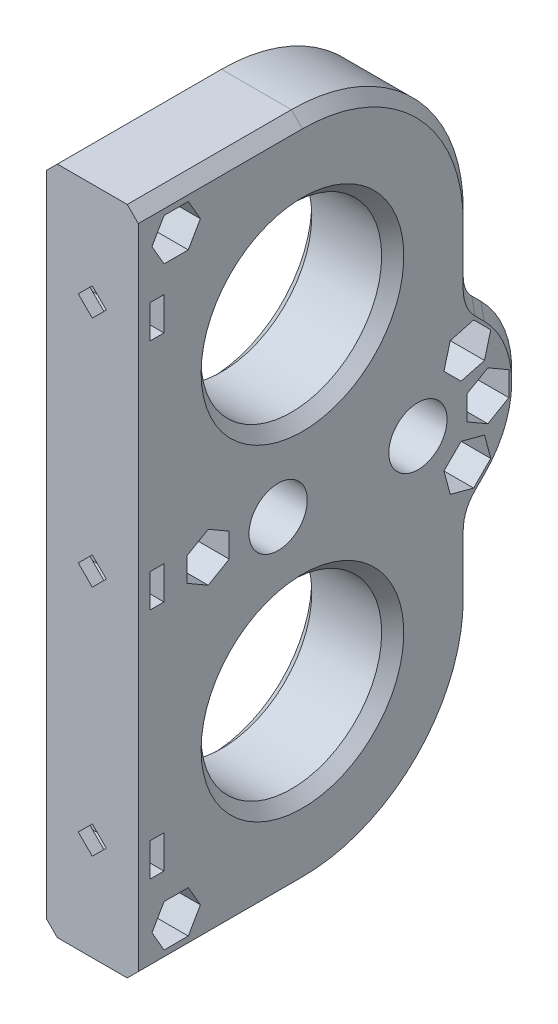
SolidWorks part; units mm, degrees
ref_plane "1" through (0, 0, 0) normal (0, 0, 1) x (1, 0, 0)
ref_plane "2" through (0, 0, 0) normal (0, 1, 0) x (1, 0, 0)
ref_plane "3" through (0, 0, 0) normal (1, 0, 0) x (0, 0, -1)
ref_plane "Front Plane" through (0, 0, 0) normal (0, -1, 0) x (1, 0, 0)
ref_plane "Right Plane" through (0, 0, 0) normal (1, 0, 0) x (0, 1, 0)
ref_plane "Top Plane" through (0, 0, 0) normal (0, 0, 1) x (1, 0, 0)
imported_body "Imported1" [suppressed]
move or copy body "Body-Move/Copy1" [suppressed] bodies to move or copy 110 copy no rotation origin (0, 0, 0) rotation axis (1, 0, 0) rotation angle 90
move or copy body "Body-Move/Copy2" [suppressed] bodies to move or copy 111 copy no translate (0, 0, 4.1741) parameters "D1"=0, "D2"=0, "D3"=4.1741
move or copy body "Body-Move/Copy3" [suppressed] bodies to move or copy 112 copy no translate (0, 0, 80) parameters "D1"=0, "D2"=0, "D3"=80
sketch "Sketch1" plane through (0, 0, 0) normal (1, 0, 0) x (0, 1, 0)
  line L0 (-28, 0) -> (0, -91.8259) construction
  line L1 (0, -91.8259) -> (28, 0) construction
  line L2 (-28, 0) -> (28, 0) construction
  line L3 (0, -91.8259) -> (0, -105.6378) construction
  line L4 (-28, -22.5) -> (-28, 0) construction
  line L11 (-8.4853, -28.3112) -> (-4.9497, -24.7757) construction
  line L12 (0, -31.8259) -> (0, -26.8259) construction
  line L13 (8.4853, -28.3112) -> (4.9497, -24.7757) construction
  line L14 (-47.4856, 11.25) -> (-28, 0) construction
  circle A0 centre (-28, 0) radius 22.5 construction
  arc A1 (-28, 0) -> (28, 0) centre (0, -91.8259) cw construction
  circle A2 centre (0, -19.8259) radius 7 construction
  circle A3 centre (0, 16.1741) radius 2 construction
  circle A7 centre (-8.4853, -28.3112) radius 2 construction
  circle A8 centre (0, -31.8259) radius 2 construction
  circle A9 centre (8.4853, -28.3112) radius 2 construction
  circle A10 centre (-47.4856, 11.25) radius 1.25 construction
  dimension "D1" = 96
  dimension "D2" = 45
  dimension "D4" = 108
  dimension "D5" = 4
  dimension "D6" = 72
  dimension "D7" = 14
  dimension "D10" = 12
  dimension "D12" = 2.5
  dimension "D3" = 56
  dimension "D8" = 45
  dimension "D9" = 45
  dimension "D11" = 120
sketch "Sketch2" plane through (0, 0, 0) normal (1, 0, 0) x (0, 1, 0)
  line L6 (-12.7279, -32.5538) -> (-14.3173, -30.9645)
  line L7 (0, 28.1741) -> (0, -37.8259)
  line L8 (0, -91.8259) -> (0, -105.6378) construction
  line L9 (-28, -29.5) -> (-17.8528, -29.5)
  line L10 (-57.5, 0) -> (-57.5, 28.1741)
  line L11 (-57.5, 28.1741) -> (0, 28.1741)
  circle A2 centre (0, -19.8259) radius 7 construction
  arc A3 (-57.5, 0) -> (-28, -29.5) centre (-28, 0) ccw
  arc A4 (0, -37.8259) -> (-12.7279, -32.5538) centre (0, -19.8259) cw
  circle A5 centre (-28, 0) radius 22.5 construction
  arc A6 (-17.8528, -29.5) -> (-14.3173, -30.9645) centre (-17.8528, -34.5) cw
  point P5 (-51.2991, 11.1306)
  dimension "D2" = 18
  dimension "D3" = 57.5
  dimension "D4" = 5
  dimension "D5" = 48
  dimension "D1" = 45
extrude "Boss-Extrude1" add sketch "Sketch2" against normal mid plane 16 separate body
sketch "Sketch9" plane through (0, 0, 0) normal (1, 0, 0) x (0, 1, 0)
  line L0 (0, 4.1741) -> (0, -19.8259) construction
  circle A5 centre (0, 4.1741) radius 5
  circle A6 centre (0, -19.8259) radius 5
  arc A7 (28, 0) -> (-28, 0) centre (0, -91.8259) ccw construction
  dimension "D2" = 96
  dimension "D1" = 10
  dimension "D3" = 24
extrude "Cut-Extrude1" cut sketch "Sketch9" along normal through all both and the other way through all from surface starting at face at (-8, -24.2983, -13.8775)
sketch "Sketch10" plane through (0, 0, 0) normal (1, 0, 0) x (0, 1, 0)
  line L0 (0, -91.8259) -> (0, -105.6378) construction
  line L1 (2.0785, 12.5741) -> (4.1569, 16.1741)
  line L2 (4.1569, 16.1741) -> (2.0785, 19.7741)
  line L3 (2.0785, 19.7741) -> (-2.0785, 19.7741)
  line L4 (-2.0785, 19.7741) -> (-4.1569, 16.1741)
  line L5 (-4.1569, 16.1741) -> (-2.0785, 12.5741)
  line L6 (-2.0785, 12.5741) -> (2.0785, 12.5741)
  line L7 (-5.5459, -31.2506) -> (-4.47, -27.2353)
  line L8 (-4.47, -27.2353) -> (-7.4094, -24.2959)
  line L9 (-7.4094, -24.2959) -> (-11.4247, -25.3718)
  line L10 (-11.4247, -25.3718) -> (-12.5006, -29.3871)
  line L11 (-12.5006, -29.3871) -> (-9.5612, -32.3265)
  line L12 (-9.5612, -32.3265) -> (-5.5459, -31.2506)
  line L13 (4.1569, -31.8259) -> (2.0785, -28.2259)
  line L14 (2.0785, -28.2259) -> (-2.0785, -28.2259)
  line L15 (-2.0785, -28.2259) -> (-4.1569, -31.8259)
  line L16 (-4.1569, -31.8259) -> (-2.0785, -35.4259)
  line L17 (-2.0785, -35.4259) -> (2.0785, -35.4259)
  line L18 (2.0785, -35.4259) -> (4.1569, -31.8259)
  line L19 (12.5006, -29.3871) -> (11.4247, -25.3718)
  line L20 (11.4247, -25.3718) -> (7.4094, -24.2959)
  line L21 (7.4094, -24.2959) -> (4.47, -27.2353)
  line L22 (4.47, -27.2353) -> (5.5459, -31.2506)
  line L23 (5.5459, -31.2506) -> (9.5612, -32.3265)
  line L24 (9.5612, -32.3265) -> (12.5006, -29.3871)
  line L25 (-8.4853, -28.3112) -> (-4.9497, -24.7757) construction
  line L26 (0, -31.8259) -> (0, -26.8259) construction
  line L27 (8.4853, -28.3112) -> (4.9497, -24.7757) construction
  line L29 (-51, 17.5172) -> (-47.4, 19.5956)
  line L30 (-47.4, 19.5956) -> (-47.4, 23.7525)
  line L31 (-47.4, 23.7525) -> (-51, 25.831)
  line L32 (-51, 25.831) -> (-54.6, 23.7525)
  line L33 (-54.6, 23.7525) -> (-54.6, 19.5956)
  line L34 (-54.6, 19.5956) -> (-51, 17.5172)
  circle A0 centre (0, 16.1741) radius 3.6 construction
  circle A1 centre (-8.4853, -28.3112) radius 3.6 construction
  circle A2 centre (0, -31.8259) radius 3.6 construction
  circle A3 centre (8.4853, -28.3112) radius 3.6 construction
  circle A4 centre (0, 16.1741) radius 2 construction
  circle A5 centre (-8.4853, -28.3112) radius 2 construction
  circle A6 centre (0, -31.8259) radius 2 construction
  circle A7 centre (8.4853, -28.3112) radius 2 construction
  circle A8 centre (-51, 21.6741) radius 3.6 construction
  circle A11 centre (0, -19.8259) radius 7 construction
  dimension "D1" = 7.2
  dimension "D2" = 41.5
  dimension "D3" = 51
extrude "Cut-Extrude2" cut sketch "Sketch10" against normal through all both and the other way through all
sketch "Sketch11" plane through (0, 0, 0) normal (1, 0, 0) x (0, 1, 0)
  circle A0 centre (-28, 0) radius 15.5
  circle A1 centre (-28, 0) radius 22.5 construction
  dimension "D1" = 31
extrude "Cut-Extrude3" cut sketch "Sketch11" against normal through all both and the other way through all
sketch "Sketch12" plane through (0, 0, 0) normal (1, 0, 0) x (0, 1, 0)
  line L0 (-42.85, 26.1741) -> (-37.15, 26.1741)
  line L1 (-42.85, 26.1741) -> (-42.85, 23.7741)
  line L2 (-37.15, 26.1741) -> (-37.15, 23.7741)
  line L3 (-42.85, 23.7741) -> (-37.15, 23.7741)
  line L4 (-2.85, 26.1741) -> (2.85, 26.1741)
  line L5 (-2.85, 26.1741) -> (-2.85, 23.7741)
  line L6 (2.85, 26.1741) -> (2.85, 23.7741)
  line L7 (-2.85, 23.7741) -> (2.85, 23.7741)
  line L8 (-40, 26.1741) -> (-40, 31.3729) construction
  line L9 (0, 26.1741) -> (0, 32.0045) construction
  circle A0 centre (0, -19.8259) radius 7 construction
  point P15 (0, 32.0045)
  point P16 (-40, 31.3729)
  dimension "D4" = 46
  dimension "D1" = 40
  dimension "D2" = 2.4
  dimension "D3" = 5.7
extrude "Cut-Extrude4" cut sketch "Sketch12" against normal through all both and the other way through all
sketch "Sketch13" plane through (0, 0, 0) normal (0, 0, 1) x (1, 0, 0)
  line L8 (0, -2.4042) -> (0, -37.5958) construction
  line L9 (0, -2.4042) -> (2.4042, 0)
  line L10 (2.4042, 0) -> (0, 2.4042)
  line L11 (0, 2.4042) -> (-2.4042, 0)
  line L12 (-2.4042, 0) -> (0, -2.4042)
  line L13 (0, -42.4042) -> (2.4042, -40)
  line L14 (2.4042, -40) -> (0, -37.5958)
  line L15 (0, -37.5958) -> (-2.4042, -40)
  line L16 (-2.4042, -40) -> (0, -42.4042)
  line L17 (0, 2.4042) -> (0, 0) construction
  line L18 (0, -42.4042) -> (0, -40) construction
  circle A0 centre (0, 0) radius 1.7 construction
  circle A1 centre (0, -40) radius 1.7 construction
  point P7 (0, 0)
  dimension "D1" = 3.4
  dimension "D2" = 40
extrude "Cut-Extrude5" cut sketch "Sketch13" against normal blind 6 from surface starting at face at (0, -28.75, 28.1741)
chamfer "Chamfer1" distance 2 angle 45 14 edges at (-8, -6.8883, -36.4558) (-8, -13.5226, -31.7592) (-8, -15.9394, -29.8806) (-8, -22.9264, -29.5) (-8, -48.8597, -20.8597) (-8, -57.5, 14.087) (8, -6.8883, -36.4558) (8, -13.5226, -31.7592) (8, -15.9394, -29.8806) (8, -22.9264, -29.5) (8, -48.8597, -20.8597) (8, -57.5, 14.087) (8, -28, -15.5) (-8, -28, -15.5)
other "Move Face1" flip direction yes face at (-8, -28, 17.5) face at (8, -28, 17.5) offset 0.1 parameters "D1"=0.1
mirror "Mirror1" about plane through (0, 0, 0) normal (0, -1, 0) of bodies 102
